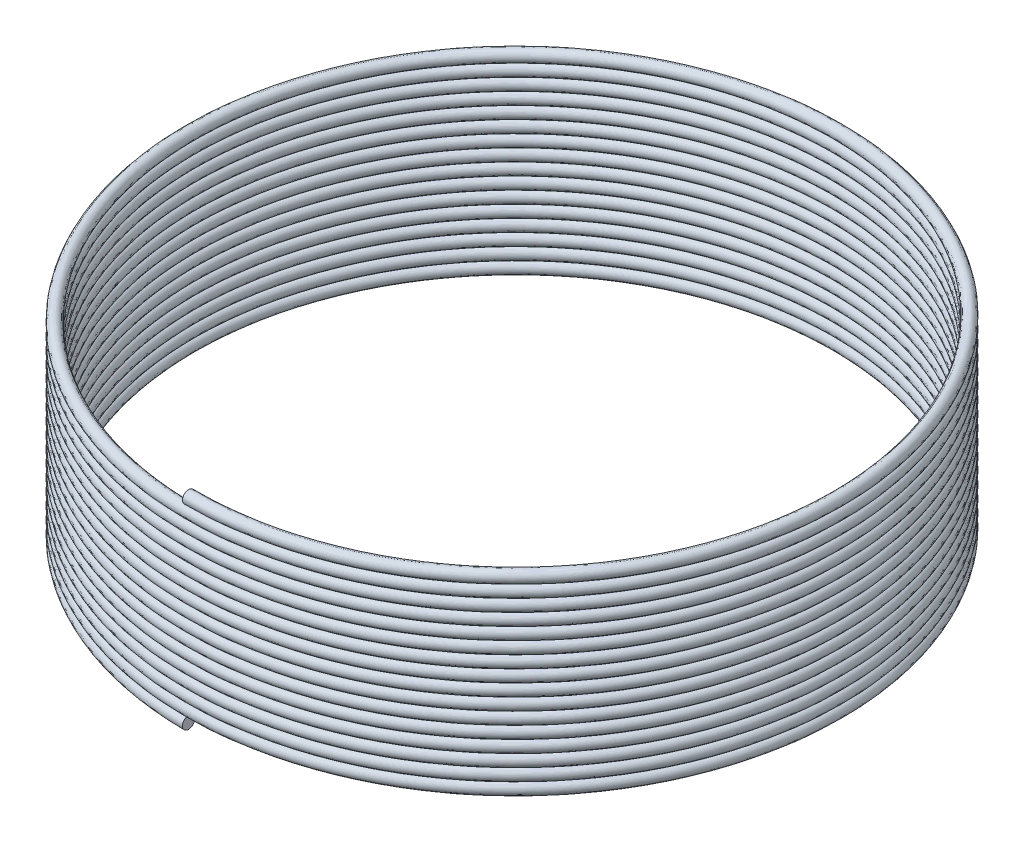
SolidWorks part; units mm, degrees
ref_plane "Front Plane" through (0, 0, 0) normal (0, 0, 1) x (1, 0, 0)
ref_plane "Top Plane" through (0, 0, 0) normal (0, 1, 0) x (1, 0, 0)
ref_plane "Right Plane" through (0, 0, 0) normal (1, 0, 0) x (0, 0, -1)
sketch "Center Axis" plane through (0, 0, 0) normal (1, 0, 0) x (0, 0, -1)
  line L0 (0, 0) -> (0, 49.506) construction
sketch "Diameter Stowed" plane through (0, 0, 0) normal (0, 1, 0) x (1, 0, 0)
  circle A0 centre (0, 0) radius 21.5
  dimension "D1" = 43
sketch "Diameter Deployed" [suppressed] plane through (0, 0, 0) normal (0, 1, 0) x (1, 0, 0)
  circle A0 centre (0, 0) radius 20
  dimension "D1" = 40
sketch "Wire Gauge XZ" plane through (0, 0, 0) normal (0, 1, 0) x (1, 0, 0)
  circle A0 centre (0, 0) radius 0.405
  dimension "D1" = 0.81
sketch "Wire Gauge YZ" plane through (0, 0, 0) normal (1, 0, 0) x (0, 0, -1)
  line L0 (0.405, 0) -> (-0.405, 0) construction
  line L1 (0, 0) -> (-0.405, 0) construction
  circle A0 centre (0, 0) radius 0.405
curve "Deployed Helix" [suppressed] pitch 31.75 height 508 turns 16
curve "Stowed Helix" pitch 0.8125 height 13 radius 21.5 left hand yes centre (0, 0, 0) axis (0, 1, 0) start towards (0, 0, 1)
sketch "Sketch7" [suppressed] plane through (0, 0, 0) normal (1, 0, 0) x (0, 0, -1)
  circle A0 centre (-20, 0) radius 0.405
  circle A1 centre (0, 0) radius 0.405 construction
  spline S0 degree 3 poles (-20, 0) (-20, 0.5255) (-19.3408, 1.5835) (-16.4704, 3.1649) (-11.9977, 4.7477) (-6.3578, 6.3302) (-0.0995, 7.9128) (6.1686, 9.4953) (11.8365, 11.0779) (16.3529, 12.6604) (19.2785, 14.243) (20.3286, 15.8255) (19.4011, 17.4081) (16.5862, 18.9907) (12.1577, 20.5732) (6.5465, 22.1558) (0.2984, 23.7383) (-5.9787, 25.3209) (-11.6742, 26.9034) (-16.234, 28.486) (-19.2145, 30.0685) (-20.3257, 31.6511) (-19.4596, 33.2336) (-16.7005, 34.8162) (-12.3166, 36.3988) (-6.7346, 37.9813) (-0.4974, 39.5639) (5.7882, 41.1464) (11.5107, 42.729) (16.1134, 44.3115) (19.1486, 45.8941) (20.3209, 47.4766) (19.5163, 49.0592) (16.8131, 50.6417) (12.4743, 52.2243) (6.922, 53.8069) (0.6962, 55.3894) (-5.5972, 56.972) (-11.3462, 58.5545) (-15.9913, 60.1371) (-19.0808, 61.7196) (-20.314, 63.3022) (-19.5711, 64.8847) (-16.9242, 66.4673) (-12.6308, 68.0498) (-7.1087, 69.6324) (-0.895, 71.215) (5.4057, 72.7975) (11.1805, 74.3801) (15.8677, 75.9626) (19.0112, 77.5452) (20.3053, 79.1277) (19.624, 80.7103) (17.0336, 82.2928) (12.7861, 83.8754) (7.2948, 85.4579) (1.0938, 87.0405) (-5.2136, 88.6231) (-11.0138, 90.2056) (-15.7426, 91.7882) (-18.9398, 93.3707) (-20.2946, 94.9533) (-19.675, 96.5358) (-17.1414, 98.1184) (-12.9402, 99.7009) (-7.4801, 101.2835) (-1.2924, 102.866) (5.0211, 104.4486) (10.8461, 106.0312) (15.6159, 107.6137) (18.8666, 109.1963) (20.2819, 110.7788) (19.7241, 112.3614) (17.2475, 113.9439) (13.093, 115.5265) (7.6648, 117.109) (1.4909, 118.6916) (-4.828, 120.2741) (-10.6773, 121.8567) (-15.4878, 123.4393) (-18.7916, 125.0218) (-20.2673, 126.6044) (-19.7714, 128.1869) (-17.352, 129.7695) (-13.2446, 131.352) (-7.8487, 132.9346) (-1.6892, 134.5171) (4.6345, 136.0997) (10.5075, 137.6822) (15.3582, 139.2648) (18.7148, 140.8474) (20.2508, 142.4299) (19.8167, 144.0125) (17.4549, 145.595) (13.3949, 147.1776) (8.0318, 148.7601) (1.8874, 150.3427) (-4.4406, 151.9252) (-10.3366, 153.5078) (-15.2271, 155.0903) (-18.6362, 156.6729) (-20.2323, 158.2555) (-19.8602, 159.838) (-17.556, 161.4206) (-13.5439, 163.0031) (-8.2142, 164.5857) (-2.0854, 166.1682) (4.2462, 167.7508) (10.1648, 169.3333) (15.0945, 170.9159) (18.5558, 172.4984) (20.2119, 174.081) (19.9018, 175.6636) (17.6555, 177.2461) (13.6917, 178.8287) (8.3958, 180.4112) (2.2833, 181.9938) (-4.0514, 183.5763) (-9.992, 185.1589) (-14.9605, 186.7414) (-18.4736, 188.324) (-20.1896, 189.9065) (-19.9414, 191.4891) (-17.7533, 193.0717) (-13.8381, 194.6542) (-8.5766, 196.2368) (-2.4808, 197.8193) (3.8563, 199.4019) (9.8183, 200.9844) (14.8251, 202.567) (18.3897, 204.1495) (20.1653, 205.7321) (19.9792, 207.3146) (17.8494, 208.8972) (13.9832, 210.4798) (8.7566, 212.0623) (2.6782, 213.6449) (-3.6608, 215.2274) (-9.6436, 216.81) (-14.6883, 218.3925) (-18.304, 219.9751) (-20.1391, 221.5576) (-20.015, 223.1402) (-17.9438, 224.7227) (-14.1269, 226.3053) (-8.9358, 227.8879) (-2.8753, 229.4704) (3.4649, 231.053) (9.468, 232.6355) (14.55, 234.2181) (18.2166, 235.8006) (20.111, 237.3832) (20.0489, 238.9657) (18.0364, 240.5483) (14.2693, 242.1308) (9.114, 243.7134) (3.0721, 245.296) (-3.2687, 246.8785) (-9.2914, 248.4611) (-14.4103, 250.0436) (-18.1274, 251.6262) (-20.0809, 253.2087) (-20.0809, 254.7913) (-18.1274, 256.3738) (-14.4103, 257.9564) (-9.2914, 259.5389) (-3.2687, 261.1215) (3.0721, 262.704) (9.114, 264.2866) (14.2693, 265.8692) (18.0364, 267.4517) (20.0489, 269.0343) (20.111, 270.6168) (18.2166, 272.1994) (14.55, 273.7819) (9.468, 275.3645) (3.4649, 276.947) (-2.8753, 278.5296) (-8.9358, 280.1121) (-14.1269, 281.6947) (-17.9438, 283.2773) (-20.015, 284.8598) (-20.1391, 286.4424) (-18.304, 288.0249) (-14.6883, 289.6075) (-9.6436, 291.19) (-3.6608, 292.7726) (2.6782, 294.3551) (8.7566, 295.9377) (13.9832, 297.5202) (17.8494, 299.1028) (19.9792, 300.6854) (20.1653, 302.2679) (18.3897, 303.8505) (14.8251, 305.433) (9.8183, 307.0156) (3.8563, 308.5981) (-2.4808, 310.1807) (-8.5766, 311.7632) (-13.8381, 313.3458) (-17.7533, 314.9283) (-19.9414, 316.5109) (-20.1896, 318.0935) (-18.4736, 319.676) (-14.9605, 321.2586) (-9.992, 322.8411) (-4.0514, 324.4237) (2.2833, 326.0062) (8.3958, 327.5888) (13.6917, 329.1713) (17.6555, 330.7539) (19.9018, 332.3364) (20.2119, 333.919) (18.5558, 335.5016) (15.0945, 337.0841) (10.1648, 338.6667) (4.2462, 340.2492) (-2.0854, 341.8318) (-8.2142, 343.4143) (-13.5439, 344.9969) (-17.556, 346.5794) (-19.8602, 348.162) (-20.2323, 349.7445) (-18.6362, 351.3271) (-15.2271, 352.9097) (-10.3366, 354.4922) (-4.4406, 356.0748) (1.8874, 357.6573) (8.0318, 359.2399) (13.3949, 360.8224) (17.4549, 362.405) (19.8167, 363.9875) (20.2508, 365.5701) (18.7148, 367.1526) (15.3582, 368.7352) (10.5075, 370.3178) (4.6345, 371.9003) (-1.6892, 373.4829) (-7.8487, 375.0654) (-13.2446, 376.648) (-17.352, 378.2305) (-19.7714, 379.8131) (-20.2673, 381.3956) (-18.7916, 382.9782) (-15.4878, 384.5607) (-10.6773, 386.1433) (-4.828, 387.7259) (1.4909, 389.3084) (7.6648, 390.891) (13.093, 392.4735) (17.2475, 394.0561) (19.7241, 395.6386) (20.2819, 397.2212) (18.8666, 398.8037) (15.6159, 400.3863) (10.8461, 401.9688) (5.0211, 403.5514) (-1.2924, 405.134) (-7.4801, 406.7165) (-12.9402, 408.2991) (-17.1414, 409.8816) (-19.675, 411.4642) (-20.2946, 413.0467) (-18.9398, 414.6293) (-15.7426, 416.2118) (-11.0138, 417.7944) (-5.2136, 419.3769) (1.0938, 420.9595) (7.2948, 422.5421) (12.7861, 424.1246) (17.0336, 425.7072) (19.624, 427.2897) (20.3053, 428.8723) (19.0112, 430.4548) (15.8677, 432.0374) (11.1805, 433.6199) (5.4057, 435.2025) (-0.895, 436.785) (-7.1087, 438.3676) (-12.6308, 439.9502) (-16.9242, 441.5327) (-19.5711, 443.1153) (-20.314, 444.6978) (-19.0808, 446.2804) (-15.9913, 447.8629) (-11.3462, 449.4455) (-5.5972, 451.028) (0.6962, 452.6106) (6.922, 454.1931) (12.4743, 455.7757) (16.8131, 457.3583) (19.5163, 458.9408) (20.3209, 460.5234) (19.1486, 462.1059) (16.1134, 463.6885) (11.5107, 465.271) (5.7882, 466.8536) (-0.4974, 468.4361) (-6.7346, 470.0187) (-12.3166, 471.6012) (-16.7005, 473.1838) (-19.4596, 474.7664) (-20.3257, 476.3489) (-19.2145, 477.9315) (-16.234, 479.514) (-11.6742, 481.0966) (-5.9787, 482.6791) (0.2984, 484.2617) (6.5465, 485.8442) (12.1577, 487.4268) (16.5862, 489.0093) (19.4011, 490.5919) (20.3286, 492.1745) (19.2785, 493.757) (16.3529, 495.3396) (11.8365, 496.9221) (6.1686, 498.5047) (-0.0995, 500.0872) (-6.3578, 501.6698) (-11.9977, 503.2523) (-16.4704, 504.8351) (-19.3408, 506.4165) (-20, 507.4745) (-20, 508) knots 0 0 0 0 0.003115 0.006231 0.009346 0.012461 0.015576 0.018692 0.021807 0.024922 0.028037 0.031153 0.034268 0.037383 0.040498 0.043614 0.046729 0.049844 0.05296 0.056075 0.05919 0.062305 0.065421 0.068536 0.071651 0.074766 0.077882 0.080997 0.084112 0.087227 0.090343 0.093458 0.096573 0.099688 0.102804 0.105919 0.109034 0.11215 0.115265 0.11838 0.121495 0.124611 0.127726 0.130841 0.133956 0.137072 0.140187 0.143302 0.146417 0.149533 0.152648 0.155763 0.158879 0.161994 0.165109 0.168224 0.17134 0.174455 0.17757 0.180685 0.183801 0.186916 0.190031 0.193146 0.196262 0.199377 0.202492 0.205607 0.208723 0.211838 0.214953 0.218069 0.221184 0.224299 0.227414 0.23053 0.233645 0.23676 0.239875 0.242991 0.246106 0.249221 0.252336 0.255452 0.258567 0.261682 0.264798 0.267913 0.271028 0.274143 0.277259 0.280374 0.283489 0.286604 0.28972 0.292835 0.29595 0.299065 0.302181 0.305296 0.308411 0.311526 0.314642 0.317757 0.320872 0.323988 0.327103 0.330218 0.333333 0.336449 0.339564 0.342679 0.345794 0.34891 0.352025 0.35514 0.358255 0.361371 0.364486 0.367601 0.370717 0.373832 0.376947 0.380062 0.383178 0.386293 0.389408 0.392523 0.395639 0.398754 0.401869 0.404984 0.4081 0.411215 0.41433 0.417445 0.420561 0.423676 0.426791 0.429907 0.433022 0.436137 0.439252 0.442368 0.445483 0.448598 0.451713 0.454829 0.457944 0.461059 0.464174 0.46729 0.470405 0.47352 0.476636 0.479751 0.482866 0.485981 0.489097 0.492212 0.495327 0.498442 0.501558 0.504673 0.507788 0.510903 0.514019 0.517134 0.520249 0.523364 0.52648 0.529595 0.53271 0.535826 0.538941 0.542056 0.545171 0.548287 0.551402 0.554517 0.557632 0.560748 0.563863 0.566978 0.570093 0.573209 0.576324 0.579439 0.582555 0.58567 0.588785 0.5919 0.595016 0.598131 0.601246 0.604361 0.607477 0.610592 0.613707 0.616822 0.619938 0.623053 0.626168 0.629283 0.632399 0.635514 0.638629 0.641745 0.64486 0.647975 0.65109 0.654206 0.657321 0.660436 0.663551 0.666667 0.669782 0.672897 0.676012 0.679128 0.682243 0.685358 0.688474 0.691589 0.694704 0.697819 0.700935 0.70405 0.707165 0.71028 0.713396 0.716511 0.719626 0.722741 0.725857 0.728972 0.732087 0.735202 0.738318 0.741433 0.744548 0.747664 0.750779 0.753894 0.757009 0.760125 0.76324 0.766355 0.76947 0.772586 0.775701 0.778816 0.781931 0.785047 0.788162 0.791277 0.794393 0.797508 0.800623 0.803738 0.806854 0.809969 0.813084 0.816199 0.819315 0.82243 0.825545 0.82866 0.831776 0.834891 0.838006 0.841121 0.844237 0.847352 0.850467 0.853583 0.856698 0.859813 0.862928 0.866044 0.869159 0.872274 0.875389 0.878505 0.88162 0.884735 0.88785 0.890966 0.894081 0.897196 0.900312 0.903427 0.906542 0.909657 0.912773 0.915888 0.919003 0.922118 0.925234 0.928349 0.931464 0.934579 0.937695 0.94081 0.943925 0.94704 0.950156 0.953271 0.956386 0.959502 0.962617 0.965732 0.968847 0.971963 0.975078 0.978193 0.981308 0.984424 0.987539 0.990654 0.993769 0.996885 1 1 1 1 construction
sweep "Deployed" [suppressed] add profiles "Sketch7" path "Deployed Helix"
sketch "Sketch8" plane through (0, 0, 0) normal (1, 0, 0) x (0, 0, -1)
  circle A0 centre (-21.5, 0) radius 0.405
  circle A1 centre (0, 0) radius 0.405 construction
  spline S0 degree 3 poles (-21.5, 0) (-21.5, 0.0132) (-20.8215, 0.0397) (-17.863, 0.0793) (-13.2395, 0.1189) (-7.382, 0.1585) (-0.8365, 0.1982) (5.787, 0.2378) (11.8711, 0.2774) (16.8488, 0.3171) (20.256, 0.3567) (21.7752, 0.3963) (21.2648, 0.436) (18.7724, 0.4756) (14.5302, 0.5152) (8.9338, 0.5549) (2.5046, 0.5945) (-4.158, 0.6341) (-10.433, 0.6738) (-15.7357, 0.7134) (-19.5716, 0.753) (-21.5833, 0.7927) (-21.5833, 0.8323) (-19.5716, 0.872) (-15.7357, 0.9116) (-10.433, 0.9512) (-4.158, 0.9909) (2.5046, 1.0305) (8.9338, 1.0701) (14.5302, 1.1098) (18.7724, 1.1494) (21.2648, 1.189) (21.7752, 1.2287) (20.256, 1.2683) (16.8488, 1.3079) (11.8711, 1.3476) (5.787, 1.3872) (-0.8365, 1.4268) (-7.382, 1.4665) (-13.2395, 1.5061) (-17.863, 1.5457) (-20.8215, 1.5854) (-21.8393, 1.625) (-20.8215, 1.6646) (-17.863, 1.7043) (-13.2395, 1.7439) (-7.382, 1.7835) (-0.8365, 1.8232) (5.787, 1.8628) (11.8711, 1.9024) (16.8488, 1.9421) (20.256, 1.9817) (21.7752, 2.0213) (21.2648, 2.061) (18.7724, 2.1006) (14.5302, 2.1402) (8.9338, 2.1799) (2.5046, 2.2195) (-4.158, 2.2591) (-10.433, 2.2988) (-15.7357, 2.3384) (-19.5716, 2.378) (-21.5833, 2.4177) (-21.5833, 2.4573) (-19.5716, 2.497) (-15.7357, 2.5366) (-10.433, 2.5762) (-4.158, 2.6159) (2.5046, 2.6555) (8.9338, 2.6951) (14.5302, 2.7348) (18.7724, 2.7744) (21.2648, 2.814) (21.7752, 2.8537) (20.256, 2.8933) (16.8488, 2.9329) (11.8711, 2.9726) (5.787, 3.0122) (-0.8365, 3.0518) (-7.382, 3.0915) (-13.2395, 3.1311) (-17.863, 3.1707) (-20.8215, 3.2104) (-21.8393, 3.25) (-20.8215, 3.2896) (-17.863, 3.3293) (-13.2395, 3.3689) (-7.382, 3.4085) (-0.8365, 3.4482) (5.787, 3.4878) (11.8711, 3.5274) (16.8488, 3.5671) (20.256, 3.6067) (21.7752, 3.6463) (21.2648, 3.686) (18.7724, 3.7256) (14.5302, 3.7652) (8.9338, 3.8049) (2.5046, 3.8445) (-4.158, 3.8841) (-10.433, 3.9238) (-15.7357, 3.9634) (-19.5716, 4.003) (-21.5833, 4.0427) (-21.5833, 4.0823) (-19.5716, 4.122) (-15.7357, 4.1616) (-10.433, 4.2012) (-4.158, 4.2409) (2.5046, 4.2805) (8.9338, 4.3201) (14.5302, 4.3598) (18.7724, 4.3994) (21.2648, 4.439) (21.7752, 4.4787) (20.256, 4.5183) (16.8488, 4.5579) (11.8711, 4.5976) (5.787, 4.6372) (-0.8365, 4.6768) (-7.382, 4.7165) (-13.2395, 4.7561) (-17.863, 4.7957) (-20.8215, 4.8354) (-21.8393, 4.875) (-20.8215, 4.9146) (-17.863, 4.9543) (-13.2395, 4.9939) (-7.382, 5.0335) (-0.8365, 5.0732) (5.787, 5.1128) (11.8711, 5.1524) (16.8488, 5.1921) (20.256, 5.2317) (21.7752, 5.2713) (21.2648, 5.311) (18.7724, 5.3506) (14.5302, 5.3902) (8.9338, 5.4299) (2.5046, 5.4695) (-4.158, 5.5091) (-10.433, 5.5488) (-15.7357, 5.5884) (-19.5716, 5.628) (-21.5833, 5.6677) (-21.5833, 5.7073) (-19.5716, 5.747) (-15.7357, 5.7866) (-10.433, 5.8262) (-4.158, 5.8659) (2.5046, 5.9055) (8.9338, 5.9451) (14.5302, 5.9848) (18.7724, 6.0244) (21.2648, 6.064) (21.7752, 6.1037) (20.256, 6.1433) (16.8488, 6.1829) (11.8711, 6.2226) (5.787, 6.2622) (-0.8365, 6.3018) (-7.382, 6.3415) (-13.2395, 6.3811) (-17.863, 6.4207) (-20.8215, 6.4604) (-21.8393, 6.5) (-20.8215, 6.5396) (-17.863, 6.5793) (-13.2395, 6.6189) (-7.382, 6.6585) (-0.8365, 6.6982) (5.787, 6.7378) (11.8711, 6.7774) (16.8488, 6.8171) (20.256, 6.8567) (21.7752, 6.8963) (21.2648, 6.936) (18.7724, 6.9756) (14.5302, 7.0152) (8.9338, 7.0549) (2.5046, 7.0945) (-4.158, 7.1341) (-10.433, 7.1738) (-15.7357, 7.2134) (-19.5716, 7.253) (-21.5833, 7.2927) (-21.5833, 7.3323) (-19.5716, 7.372) (-15.7357, 7.4116) (-10.433, 7.4512) (-4.158, 7.4909) (2.5046, 7.5305) (8.9338, 7.5701) (14.5302, 7.6098) (18.7724, 7.6494) (21.2648, 7.689) (21.7752, 7.7287) (20.256, 7.7683) (16.8488, 7.8079) (11.8711, 7.8476) (5.787, 7.8872) (-0.8365, 7.9268) (-7.382, 7.9665) (-13.2395, 8.0061) (-17.863, 8.0457) (-20.8215, 8.0854) (-21.8393, 8.125) (-20.8215, 8.1646) (-17.863, 8.2043) (-13.2395, 8.2439) (-7.382, 8.2835) (-0.8365, 8.3232) (5.787, 8.3628) (11.8711, 8.4024) (16.8488, 8.4421) (20.256, 8.4817) (21.7752, 8.5213) (21.2648, 8.561) (18.7724, 8.6006) (14.5302, 8.6402) (8.9338, 8.6799) (2.5046, 8.7195) (-4.158, 8.7591) (-10.433, 8.7988) (-15.7357, 8.8384) (-19.5716, 8.878) (-21.5833, 8.9177) (-21.5833, 8.9573) (-19.5716, 8.997) (-15.7357, 9.0366) (-10.433, 9.0762) (-4.158, 9.1159) (2.5046, 9.1555) (8.9338, 9.1951) (14.5302, 9.2348) (18.7724, 9.2744) (21.2648, 9.314) (21.7752, 9.3537) (20.256, 9.3933) (16.8488, 9.4329) (11.8711, 9.4726) (5.787, 9.5122) (-0.8365, 9.5518) (-7.382, 9.5915) (-13.2395, 9.6311) (-17.863, 9.6707) (-20.8215, 9.7104) (-21.8393, 9.75) (-20.8215, 9.7896) (-17.863, 9.8293) (-13.2395, 9.8689) (-7.382, 9.9085) (-0.8365, 9.9482) (5.787, 9.9878) (11.8711, 10.0274) (16.8488, 10.0671) (20.256, 10.1067) (21.7752, 10.1463) (21.2648, 10.186) (18.7724, 10.2256) (14.5302, 10.2652) (8.9338, 10.3049) (2.5046, 10.3445) (-4.158, 10.3841) (-10.433, 10.4238) (-15.7357, 10.4634) (-19.5716, 10.503) (-21.5833, 10.5427) (-21.5833, 10.5823) (-19.5716, 10.622) (-15.7357, 10.6616) (-10.433, 10.7012) (-4.158, 10.7409) (2.5046, 10.7805) (8.9338, 10.8201) (14.5302, 10.8598) (18.7724, 10.8994) (21.2648, 10.939) (21.7752, 10.9787) (20.256, 11.0183) (16.8488, 11.0579) (11.8711, 11.0976) (5.787, 11.1372) (-0.8365, 11.1768) (-7.382, 11.2165) (-13.2395, 11.2561) (-17.863, 11.2957) (-20.8215, 11.3354) (-21.8393, 11.375) (-20.8215, 11.4146) (-17.863, 11.4543) (-13.2395, 11.4939) (-7.382, 11.5335) (-0.8365, 11.5732) (5.787, 11.6128) (11.8711, 11.6524) (16.8488, 11.6921) (20.256, 11.7317) (21.7752, 11.7713) (21.2648, 11.811) (18.7724, 11.8506) (14.5302, 11.8902) (8.9338, 11.9299) (2.5046, 11.9695) (-4.158, 12.0091) (-10.433, 12.0488) (-15.7357, 12.0884) (-19.5716, 12.128) (-21.5833, 12.1677) (-21.5833, 12.2073) (-19.5716, 12.247) (-15.7357, 12.2866) (-10.433, 12.3262) (-4.158, 12.3659) (2.5046, 12.4055) (8.9338, 12.4451) (14.5302, 12.4848) (18.7724, 12.5244) (21.2648, 12.564) (21.7752, 12.6037) (20.256, 12.6433) (16.8488, 12.6829) (11.8711, 12.7226) (5.787, 12.7622) (-0.8365, 12.8018) (-7.382, 12.8415) (-13.2395, 12.8811) (-17.863, 12.9207) (-20.8215, 12.9603) (-21.5, 12.9868) (-21.5, 13) knots 0 0 0 0 0.003049 0.006098 0.009146 0.012195 0.015244 0.018293 0.021341 0.02439 0.027439 0.030488 0.033537 0.036585 0.039634 0.042683 0.045732 0.04878 0.051829 0.054878 0.057927 0.060976 0.064024 0.067073 0.070122 0.073171 0.07622 0.079268 0.082317 0.085366 0.088415 0.091463 0.094512 0.097561 0.10061 0.103659 0.106707 0.109756 0.112805 0.115854 0.118902 0.121951 0.125 0.128049 0.131098 0.134146 0.137195 0.140244 0.143293 0.146341 0.14939 0.152439 0.155488 0.158537 0.161585 0.164634 0.167683 0.170732 0.17378 0.176829 0.179878 0.182927 0.185976 0.189024 0.192073 0.195122 0.198171 0.20122 0.204268 0.207317 0.210366 0.213415 0.216463 0.219512 0.222561 0.22561 0.228659 0.231707 0.234756 0.237805 0.240854 0.243902 0.246951 0.25 0.253049 0.256098 0.259146 0.262195 0.265244 0.268293 0.271341 0.27439 0.277439 0.280488 0.283537 0.286585 0.289634 0.292683 0.295732 0.29878 0.301829 0.304878 0.307927 0.310976 0.314024 0.317073 0.320122 0.323171 0.32622 0.329268 0.332317 0.335366 0.338415 0.341463 0.344512 0.347561 0.35061 0.353659 0.356707 0.359756 0.362805 0.365854 0.368902 0.371951 0.375 0.378049 0.381098 0.384146 0.387195 0.390244 0.393293 0.396341 0.39939 0.402439 0.405488 0.408537 0.411585 0.414634 0.417683 0.420732 0.42378 0.426829 0.429878 0.432927 0.435976 0.439024 0.442073 0.445122 0.448171 0.45122 0.454268 0.457317 0.460366 0.463415 0.466463 0.469512 0.472561 0.47561 0.478659 0.481707 0.484756 0.487805 0.490854 0.493902 0.496951 0.5 0.503049 0.506098 0.509146 0.512195 0.515244 0.518293 0.521341 0.52439 0.527439 0.530488 0.533537 0.536585 0.539634 0.542683 0.545732 0.54878 0.551829 0.554878 0.557927 0.560976 0.564024 0.567073 0.570122 0.573171 0.57622 0.579268 0.582317 0.585366 0.588415 0.591463 0.594512 0.597561 0.60061 0.603659 0.606707 0.609756 0.612805 0.615854 0.618902 0.621951 0.625 0.628049 0.631098 0.634146 0.637195 0.640244 0.643293 0.646341 0.64939 0.652439 0.655488 0.658537 0.661585 0.664634 0.667683 0.670732 0.67378 0.676829 0.679878 0.682927 0.685976 0.689024 0.692073 0.695122 0.698171 0.70122 0.704268 0.707317 0.710366 0.713415 0.716463 0.719512 0.722561 0.72561 0.728659 0.731707 0.734756 0.737805 0.740854 0.743902 0.746951 0.75 0.753049 0.756098 0.759146 0.762195 0.765244 0.768293 0.771341 0.77439 0.777439 0.780488 0.783537 0.786585 0.789634 0.792683 0.795732 0.79878 0.801829 0.804878 0.807927 0.810976 0.814024 0.817073 0.820122 0.823171 0.82622 0.829268 0.832317 0.835366 0.838415 0.841463 0.844512 0.847561 0.85061 0.853659 0.856707 0.859756 0.862805 0.865854 0.868902 0.871951 0.875 0.878049 0.881098 0.884146 0.887195 0.890244 0.893293 0.896341 0.89939 0.902439 0.905488 0.908537 0.911585 0.914634 0.917683 0.920732 0.92378 0.926829 0.929878 0.932927 0.935976 0.939024 0.942073 0.945122 0.948171 0.95122 0.954268 0.957317 0.960366 0.963415 0.966463 0.969512 0.972561 0.97561 0.978659 0.981707 0.984756 0.987805 0.990854 0.993902 0.996951 1 1 1 1 construction
  point P2 (0, 0)
  point P4 (0, 0)
  point P5 (0, 0)
sweep "Stowed" add profiles "Sketch8" path "Stowed Helix"
